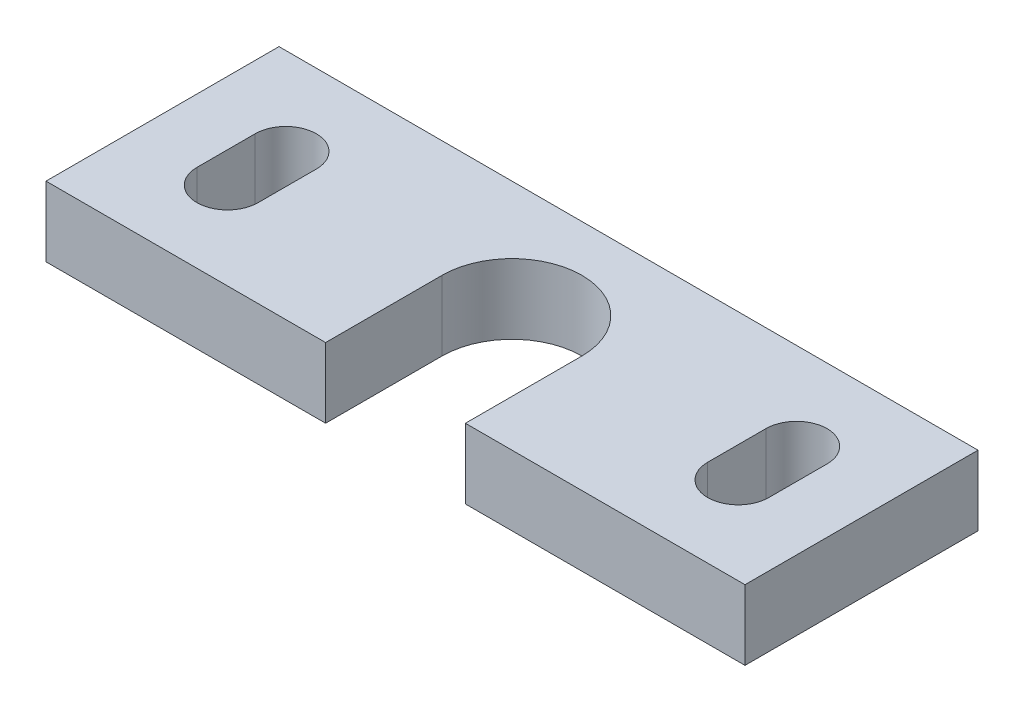
SolidWorks part; units mm, degrees
ref_plane "Front Plane" through (0, 0, 0) normal (0, 0, 1) x (1, 0, 0)
ref_plane "Top Plane" through (0, 0, 0) normal (0, 1, 0) x (1, 0, 0)
ref_plane "Right Plane" through (0, 0, 0) normal (1, 0, 0) x (0, 0, -1)
sketch "Sketch1" plane through (0, 0, 0) normal (0, 1, 0) x (1, 0, 0)
  line L0 (30, 20) -> (30, 0) construction
  line L1 (0, 0) -> (24, 0)
  line L2 (0, 0) -> (0, 20)
  line L3 (0, 20) -> (60, 20)
  line L4 (60, 0) -> (60, 20)
  line L5 (0, 0) -> (60, 20) construction
  line L6 (0, 20) -> (60, 0) construction
  line L7 (24, 0) -> (24, 10)
  line L8 (36, 10) -> (36, 0)
  line L9 (8.08, 12.5) -> (8.08, 7.5) construction
  line L10 (10.705, 12.5) -> (10.705, 7.5)
  line L11 (5.455, 12.5) -> (5.455, 7.5)
  line L12 (51.92, 12.5) -> (51.92, 7.5) construction
  line L13 (49.295, 12.5) -> (49.295, 7.5)
  line L14 (54.545, 12.5) -> (54.545, 7.5)
  line L15 (36, 0) -> (60, 0)
  arc A0 (24, 10) -> (36, 10) centre (30, 10) cw
  arc A1 (10.705, 12.5) -> (5.455, 12.5) centre (8.08, 12.5) ccw
  arc A2 (5.455, 7.5) -> (10.705, 7.5) centre (8.08, 7.5) ccw
  arc A3 (49.295, 12.5) -> (54.545, 12.5) centre (51.92, 12.5) cw
  arc A4 (54.545, 7.5) -> (49.295, 7.5) centre (51.92, 7.5) cw
  point P4 (30, 10)
  point P15 (8.08, 10)
  point P22 (51.92, 10)
  dimension "D4" = 6
  dimension "D5" = 2.625
  dimension "D1" = 60
  dimension "D2" = 20
  dimension "D3" = 10
  dimension "D6" = 10
  dimension "D7" = 8.08
  dimension "D8" = 5
extrude "Boss-Extrude1" add sketch "Sketch1" along normal blind 6
